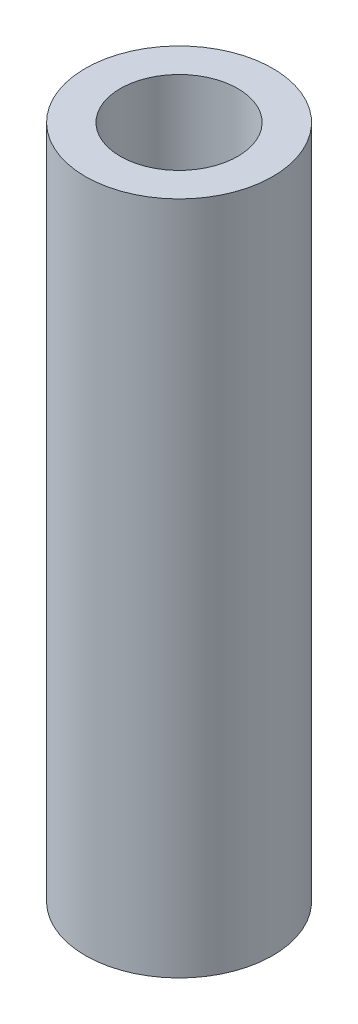
SolidWorks part; units mm, degrees
ref_plane "Front Plane" through (0, 0, 0) normal (1, 0, 0) x (0, 1, 0)
ref_plane "Top Plane" through (0, 0, 0) normal (0, 0, 1) x (0, 1, 0)
ref_plane "Right Plane" through (0, 0, 0) normal (0, 1, 0) x (-1, 0, 0)
sketch "Sketch1" plane through (0, 0, 0) normal (0, 1, 0) x (-1, 0, 0)
  circle A0 centre (0, 0) radius 3.9688
  dimension "D1" = 7.9375
extrude "Boss-Extrude1" add sketch "Sketch1" along normal blind 28.575
sketch "Sketch2" plane through (0, 28.575, 0) normal (0, 1, 0) x (-1, 0, 0)
  point P0 (0, 0)
hole_wizard "#9 (0.196) Diameter Hole1" positions "Sketch2" profile "Sketch3" hole size "#9" standard "ANSI Inch" end condition through all
sketch "Sketch3" plane through (0, 28.575, 0) normal (1, 0, 0) x (0, 0, 1)
  line L0 (0, 0) -> (0, 28.575)
  line L1 (0, 28.575) -> (2.4892, 28.575)
  line L2 (2.4892, 28.575) -> (2.4892, 0)
  line L5 (2.4892, 0) -> (0, 0)
  line L11 (0, -6.35) -> (0, 107.95) construction
  dimension "Thru Hole Dia." = 4.9784
  dimension "Thru Hole Depth" = 28.575
